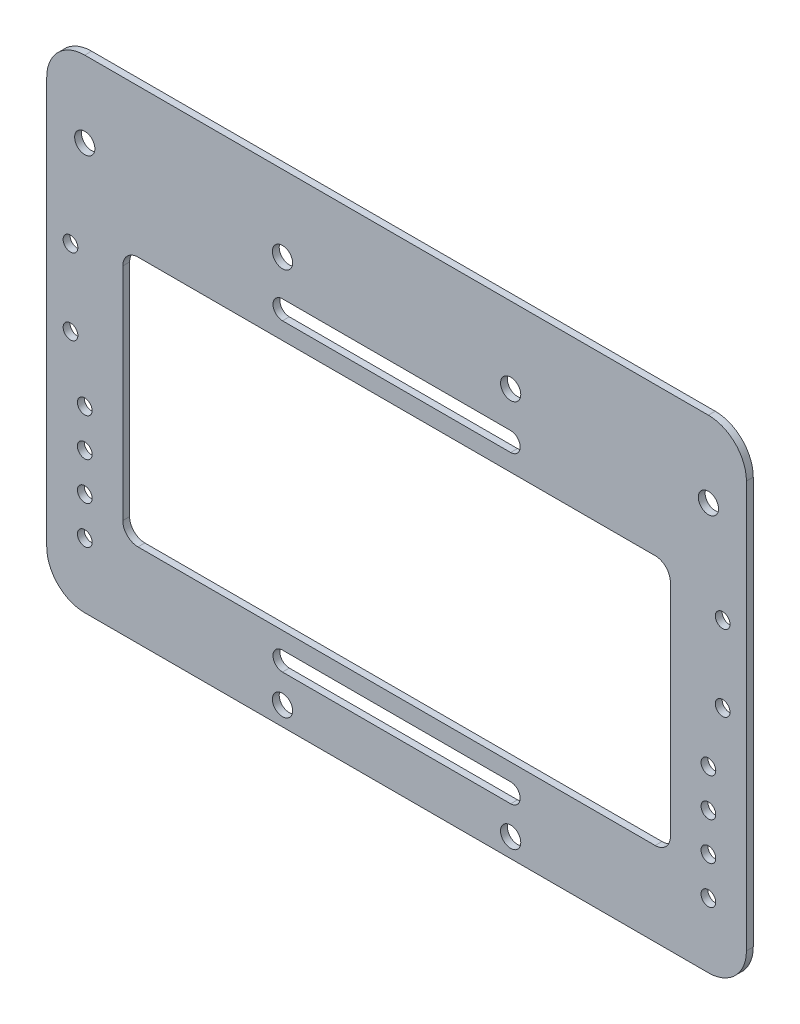
SolidWorks part; units mm, degrees
ref_plane "Front Plane" through (0, 0, 0) normal (0, 0, 1) x (1, 0, 0)
ref_plane "Top Plane" through (0, 0, 0) normal (0, 1, 0) x (1, 0, 0)
ref_plane "Right Plane" through (0, 0, 0) normal (1, 0, 0) x (0, 0, -1)
sketch "Sketch1" plane through (0, 0, 0) normal (0, 0, 1) x (1, 0, 0)
  line L1 (-116.84, 80.645) -> (116.84, 80.645)
  line L2 (-116.84, 80.645) -> (-116.84, -80.645)
  line L3 (-116.84, -80.645) -> (116.84, -80.645)
  line L4 (116.84, 80.645) -> (116.84, -80.645)
  line L5 (-116.84, 80.645) -> (116.84, -80.645) construction
  line L6 (-116.84, -80.645) -> (116.84, 80.645) construction
  line L7 (-86.36, 31.115) -> (86.36, 31.115)
  line L8 (-91.44, 26.035) -> (-91.44, -47.625)
  line L9 (-86.36, -52.705) -> (86.36, -52.705)
  line L10 (91.44, 26.035) -> (91.44, -47.625)
  line L11 (-91.44, 31.115) -> (91.44, -52.705) construction
  line L12 (-91.44, -52.705) -> (91.44, 31.115) construction
  arc A0 (86.36, -52.705) -> (91.44, -47.625) centre (86.36, -47.625) ccw
  arc A1 (86.36, 31.115) -> (91.44, 26.035) centre (86.36, 26.035) cw
  arc A2 (-91.44, 26.035) -> (-86.36, 31.115) centre (-86.36, 26.035) cw
  arc A3 (-86.36, -52.705) -> (-91.44, -47.625) centre (-86.36, -47.625) cw
  point P0 (0, 0)
  point P5 (0, -10.795)
  dimension "D7" = 5.08
  dimension "D1" = 25.4
  dimension "D2" = 161.29
  dimension "D3" = 182.88
  dimension "D4" = 83.82
  dimension "D5" = 27.94
  dimension "D6" = 233.68
extrude "Boss-Extrude1" add sketch "Sketch1" along normal blind 2.286
sketch "Sketch2" plane through (0, 0, 2.286) normal (0, 0, 1) x (1, 0, 0)
  line L0 (38.1, 40.005) -> (-38.1, 40.005) construction
  line L1 (38.1, 36.83) -> (-38.1, 36.83)
  line L2 (38.1, 43.18) -> (-38.1, 43.18)
  line L3 (-91.44, 26.035) -> (-91.44, -47.625) construction
  line L4 (-91.44, -10.795) -> (91.44, -10.795) construction
  line L5 (-91.44, 26.035) -> (-91.44, -47.625) construction
  line L6 (91.44, -47.625) -> (91.44, 26.035) construction
  line L7 (38.1, -61.595) -> (-38.1, -61.595) construction
  line L8 (38.1, -58.42) -> (-38.1, -58.42)
  line L9 (38.1, -64.77) -> (-38.1, -64.77)
  arc A0 (38.1, 36.83) -> (38.1, 43.18) centre (38.1, 40.005) ccw
  arc A1 (-38.1, 43.18) -> (-38.1, 36.83) centre (-38.1, 40.005) ccw
  arc A2 (38.1, -58.42) -> (38.1, -64.77) centre (38.1, -61.595) cw
  arc A3 (-38.1, -64.77) -> (-38.1, -58.42) centre (-38.1, -61.595) cw
  point P2 (0, 40.005)
  point P7 (-91.44, -10.795)
  point P19 (0, -61.595)
  dimension "D1" = 76.2
  dimension "D2" = 50.8
  dimension "D3" = 6.35
extrude "Cut-Extrude1" cut sketch "Sketch2" against normal through all
hole_wizard "1/4 Clearance Hole1" positions "Sketch4" profile "Sketch3" hole size "1/4" standard "ANSI Inch" end condition through all
sketch "Sketch4" plane through (0, 0, 2.286) normal (0, 0, 1) x (1, 0, 0)
  line L2 (116.84, 80.645) -> (-116.84, 80.645) construction
  line L3 (-38.1, 55.245) -> (38.1, 55.245) construction
  line L4 (-116.84, -80.645) -> (116.84, -80.645) construction
  line L6 (-38.1, -74.295) -> (38.1, -74.295) construction
  line L8 (-116.84, 80.645) -> (-116.84, -80.645) construction
  point P0 (-38.1, 55.245)
  point P8 (38.1, 55.245)
  point P22 (0, 55.245)
  point P24 (-38.1, -74.295)
  point P26 (38.1, -74.295)
  dimension "D1" = 76.2
  dimension "D2" = 6.35
  dimension "D3" = 25.4
  dimension "D4" = 76.2
  dimension "D5" = 78.74
sketch "Sketch3" plane through (-38.1, 55.245, 2.286) normal (1, 0, 0) x (0, -1, 0)
  line L0 (0, 0) -> (0, 2.286)
  line L1 (0, 2.286) -> (3.3782, 2.286)
  line L2 (3.3782, 2.286) -> (3.3782, 0)
  line L5 (3.3782, 0) -> (0, 0)
  line L11 (0, -6.35) -> (0, 107.95) construction
  dimension "Thru Hole Dia." = 6.7564
  dimension "Thru Hole Depth" = 2.286
hole_wizard "1/4 Clearance Hole2" positions "Sketch8" profile "Sketch7" hole size "1/4" standard "ANSI Inch" end condition through all
sketch "Sketch8" plane through (0, 0, 2.286) normal (0, 0, 1) x (1, 0, 0)
  line L0 (-116.84, 80.645) -> (-116.84, -80.645) construction
  line L1 (116.84, -80.645) -> (116.84, 80.645) construction
  line L2 (116.84, 80.645) -> (-116.84, 80.645) construction
  point P0 (-104.14, 55.245)
  point P2 (104.14, 55.245)
  dimension "D1" = 12.7
  dimension "D2" = 12.7
  dimension "D3" = 25.4
sketch "Sketch7" plane through (-104.14, 55.245, 2.286) normal (1, 0, 0) x (0, -1, 0)
  line L0 (0, 0) -> (0, 2.286)
  line L1 (0, 2.286) -> (3.3782, 2.286)
  line L2 (3.3782, 2.286) -> (3.3782, 0)
  line L5 (3.3782, 0) -> (0, 0)
  line L11 (0, -6.35) -> (0, 107.95) construction
  dimension "Thru Hole Dia." = 6.7564
  dimension "Thru Hole Depth" = 2.286
hole_wizard "#10 (0.1935) Diameter Hole1" positions "Sketch10" profile "Sketch9" hole size "#10" standard "ANSI Inch" end condition through all
sketch "Sketch10" plane through (0, 0, 2.286) normal (0, 0, 1) x (1, 0, 0)
  line L2 (-116.84, 80.645) -> (-116.84, -80.645) construction
  line L3 (-108.9025, -1.651) -> (-108.9025, 23.749) construction
  line L6 (-115.2525, 30.099) -> (-102.5525, 30.099) construction
  line L7 (-115.2525, 30.099) -> (-115.2525, -8.001) construction
  line L9 (-102.5525, 30.099) -> (-102.5525, -8.001) construction
  line L10 (-115.2525, 30.099) -> (-102.5525, -8.001) construction
  line L11 (-115.2525, -8.001) -> (-102.5525, 30.099) construction
  point P0 (-108.9025, 23.749)
  point P2 (-108.9025, -1.651)
  dimension "D1" = 25.4
  dimension "D3" = 7.9375
  dimension "D4" = 38.1
  dimension "D5" = 12.7
sketch "Sketch9" plane through (-108.9025, 23.749, 2.286) normal (1, 0, 0) x (0, -1, 0)
  line L0 (0, 0) -> (0, 2.286)
  line L1 (0, 2.286) -> (2.4574, 2.286)
  line L2 (2.4574, 2.286) -> (2.4574, 0)
  line L5 (2.4574, 0) -> (0, 0)
  line L11 (0, -6.35) -> (0, 107.95) construction
  dimension "Thru Hole Dia." = 4.9149
  dimension "Thru Hole Depth" = 2.286
mirror "Mirror1" about plane through (0, 0, 0) normal (1, 0, 0) of "#10 (0.1935) Diameter Hole1"
fillet "Fillet1" radius 12.7 4 edges at (-116.84, 80.645, 1.143) (116.84, 80.645, 1.143) (-116.84, -80.645, 1.143) (116.84, -80.645, 1.143)
hole_wizard "#10 (0.1935) Diameter Hole2" positions "Sketch12" profile "Sketch11" hole size "#10" standard "ANSI Inch" end condition through all
sketch "Sketch12" plane through (0, 0, 2.286) normal (0, 0, 1) x (1, 0, 0)
  line L0 (-116.84, 67.945) -> (-116.84, -67.945) construction
  line L1 (116.84, -67.945) -> (116.84, 67.945) construction
  line L2 (104.14, 80.645) -> (-104.14, 80.645) construction
  point P0 (-104.14, -20.955)
  point P2 (104.14, -20.955)
  point P17 (-104.14, -33.655)
  point P18 (104.14, -33.655)
  point P19 (-104.14, -46.355)
  point P20 (104.14, -46.355)
  point P21 (-104.14, -59.055)
  point P22 (104.14, -59.055)
  dimension "D1" = 12.7
  dimension "D2" = 12.7
  dimension "D3" = 101.6
  dimension "D4" = 4
sketch "Sketch11" plane through (-104.14, -20.955, 2.286) normal (1, 0, 0) x (0, -1, 0)
  line L0 (0, 0) -> (0, 2.286)
  line L1 (0, 2.286) -> (2.4574, 2.286)
  line L2 (2.4574, 2.286) -> (2.4574, 0)
  line L5 (2.4574, 0) -> (0, 0)
  line L11 (0, -6.35) -> (0, 107.95) construction
  dimension "Thru Hole Dia." = 4.9149
  dimension "Thru Hole Depth" = 2.286
